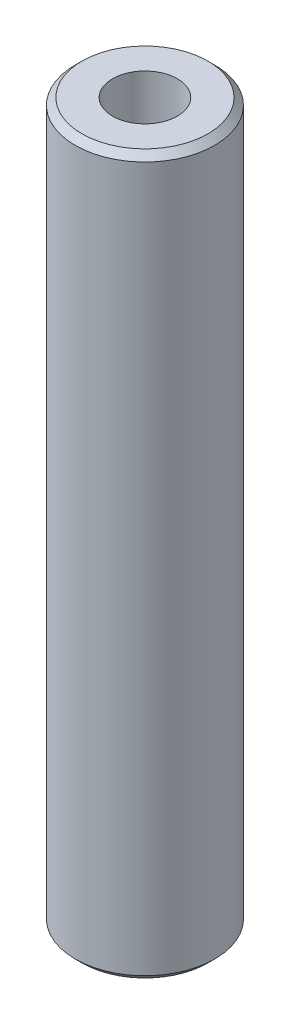
SolidWorks part; units mm, degrees
ref_plane "Front Plane" through (0, 0, 0) normal (0, 0, 1) x (1, 0, 0)
ref_plane "Top Plane" through (0, 0, 0) normal (0, 1, 0) x (1, 0, 0)
ref_plane "Right Plane" through (0, 0, 0) normal (1, 0, 0) x (0, 0, -1)
sketch "Sketch1" plane through (0, 0, 0) normal (0, 1, 0) x (1, 0, 0)
  circle A0 centre (0, 0) radius 57.5
  dimension "SHAFT_OD" = 115
extrude "Boss-Extrude1" add sketch "Sketch1" along normal blind 592.4144
sketch "Sketch2" plane through (0, 0, 0) normal (0, 1, 0) x (1, 0, 0)
  circle A0 centre (0, 0) radius 26.7376
  dimension "BORE_D" = 53.4751
extrude "Cut-Extrude1" cut sketch "Sketch2" along normal through all
chamfer "Chamfer1" distance 5.5137 angle 45 2 edges at (0, 592.4144, 57.5) (0, 0, 57.5)
